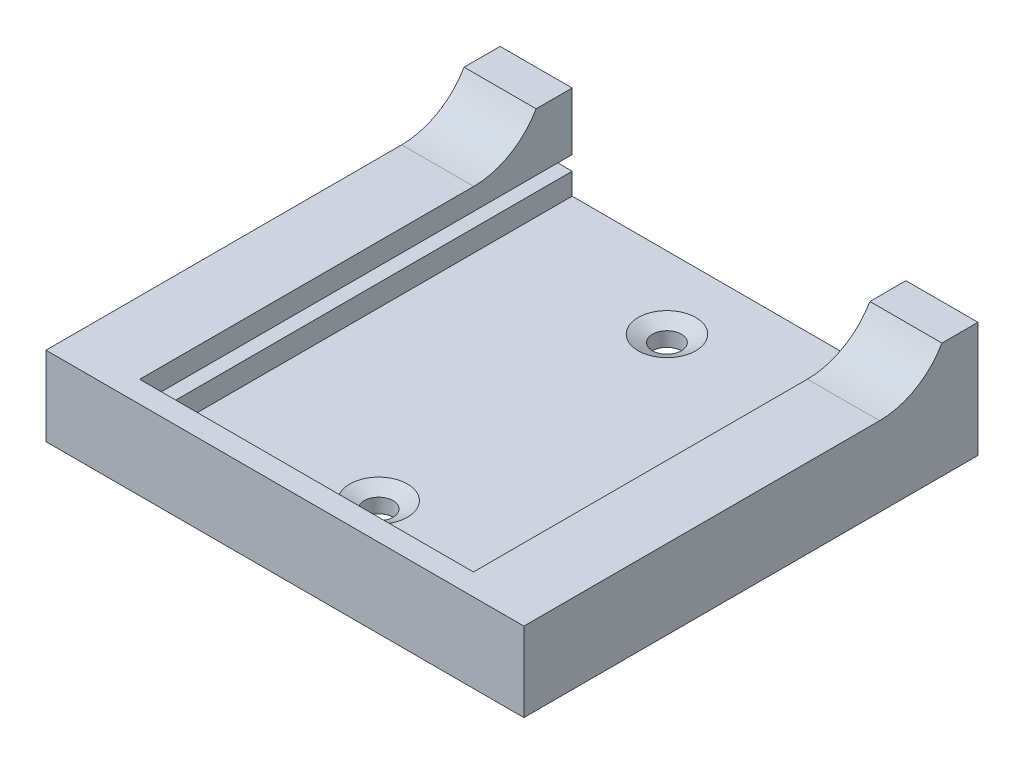
SolidWorks part; units mm, degrees
ref_plane "Спереди" through (0, 0, 0) normal (0, 0, 1) x (1, 0, 0)
ref_plane "Сверху" through (0, 0, 0) normal (0, 1, 0) x (1, 0, 0)
ref_plane "Справа" through (0, 0, 0) normal (1, 0, 0) x (0, 0, -1)
sketch "Эскиз1" plane through (0, 0, 0) normal (0, 0, 1) x (1, 0, 0)
  line L1 (0, 0) -> (66.3, 0)
  line L2 (0, 0) -> (0, 3)
  line L3 (0, 3) -> (66.3, 3)
  line L4 (66.3, 0) -> (66.3, 3)
  dimension "D1" = 66.3
  dimension "D2" = 3
extrude "base" add sketch "Эскиз1" along normal blind 60
sketch "Эскиз2" plane through (0, 0, 0) normal (0, 0, 1) x (1, 0, 0)
  line L0 (66.3, 3) -> (0, 3) construction
  line L1 (0, 3) -> (10, 3)
  line L2 (0, 3) -> (0, 11)
  line L3 (0, 11) -> (10, 11)
  line L4 (56.3, 11) -> (56.3, 8)
  line L5 (3, 6) -> (3, 8)
  line L6 (3, 8) -> (10, 8)
  line L7 (33.15, 3) -> (33.15, 0) construction
  line L8 (0, 0) -> (66.3, 0) construction
  line L9 (56.3, 6) -> (56.3, 3)
  line L10 (63.3, 6) -> (56.3, 6)
  line L11 (63.3, 8) -> (56.3, 8)
  line L12 (63.3, 6) -> (63.3, 8)
  line L13 (66.3, 11) -> (56.3, 11)
  line L14 (66.3, 3) -> (66.3, 11)
  line L15 (3, 6) -> (10, 6)
  line L16 (10, 6) -> (10, 3)
  line L17 (10, 11) -> (10, 8)
  line L18 (66.3, 3) -> (56.3, 3)
  dimension "D1" = 10
  dimension "D2" = 8
  dimension "D3" = 2
  dimension "D4" = 10
  dimension "D5" = 3
  dimension "D6" = 3
extrude "rails" add sketch "Эскиз2" along normal up to surface (60 mm away) up to face at (33.15, 1.5, 60)
sketch "Эскиз3" plane through (0, 3, 0) normal (0, 1, 0) x (1, 0, 0)
  line L0 (33.15, 0) -> (33.15, -60) construction
  line L1 (56.3, 0) -> (10, 0) construction
  line L2 (56.3, -60) -> (10, -60) construction
  circle A0 centre (33.15, -10) radius 2
  circle A1 centre (33.15, -50) radius 2
  dimension "D3" = 4
  dimension "D1" = 10
  dimension "D2" = 10
extrude "holes" cut sketch "Эскиз3" against normal through all
chamfer "Фаска1" distance 2 distance2 1 2 edges at (33.15, 3, 12) (33.15, 3, 52) first distance on face at (33.15, 3, 52)
sketch "Эскиз4" plane through (0, 0, 60) normal (0, 0, 1) x (1, 0, 0)
  line L1 (0, 11) -> (66.3, 11)
  line L2 (0, 11) -> (0, 0)
  line L3 (0, 0) -> (66.3, 0)
  line L4 (66.3, 11) -> (66.3, 0)
extrude "floor" add sketch "Эскиз4" along normal blind 3
sketch "Эскиз5" plane through (0, 11, 0) normal (0, 1, 0) x (1, 0, 0)
  line L0 (10, -60) -> (10, 0) construction
  line L1 (0, 0) -> (10, 0)
  line L2 (0, 0) -> (0, -5)
  line L3 (0, -5) -> (10, -5)
  line L4 (10, 0) -> (10, -5)
  line L5 (33.15, 0) -> (33.15, -63) construction
  line L6 (56.3, 0) -> (10, 0) construction
  line L7 (66.3, -63) -> (0, -63) construction
  line L8 (56.3, 0) -> (56.3, -5)
  line L9 (66.3, -5) -> (56.3, -5)
  line L10 (66.3, 0) -> (66.3, -5)
  line L11 (66.3, 0) -> (56.3, 0)
  dimension "D1" = 5
extrude "Вытянуть1" add sketch "Эскиз5" along normal blind 5
fillet "Скругление1" radius 10 2 edges at (61.3, 11, 5)
